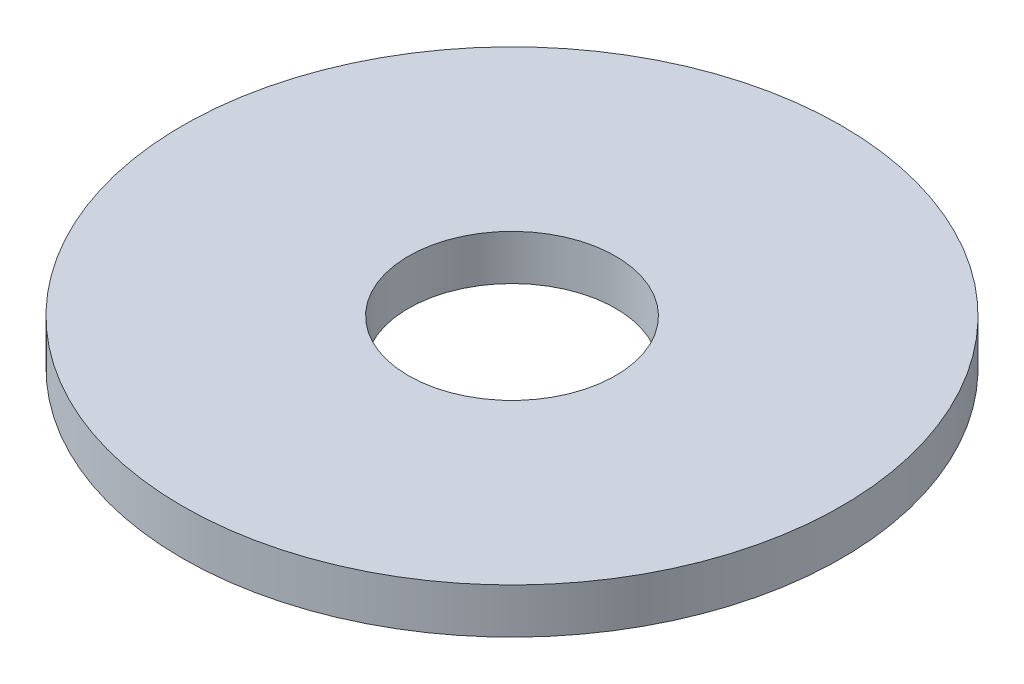
SolidWorks part; units mm, degrees
ref_plane "Front Plane" through (0, 0, 0) normal (0, 0, 1) x (1, 0, 0)
ref_plane "Top Plane" through (0, 0, 0) normal (0, 1, 0) x (1, 0, 0)
ref_plane "Right Plane" through (0, 0, 0) normal (1, 0, 0) x (0, 0, -1)
sketch "Sketch1" plane through (0, 0, 0) normal (0, 1, 0) x (1, 0, 0)
  circle A0 centre (0, 0) radius 87.5
  dimension "FLANGE_OD" = 175
extrude "Boss-Extrude1" add sketch "Sketch1" along normal blind 12
sketch "Sketch2" plane through (0, 0, 0) normal (0, 1, 0) x (1, 0, 0)
  circle A0 centre (0, 0) radius 27.5
  dimension "BORE_D" = 55
extrude "Cut-Extrude1" cut sketch "Sketch2" along normal through all
sketch "Sketch3" plane through (0, 12, 0) normal (0, 1, 0) x (1, 0, 0)
  circle A0 centre (0, 0) radius 20.168 construction
  circle A1 centre (-20.168, 0) radius 5.2138
  dimension "BOLT_D" = 10.4275
  dimension "BOLT_PCD" = 40.336
extrude "Cut-Extrude2" cut sketch "Sketch3" against normal blind 9.7605 rebuild error yes
pattern_circular "CirPattern1" count 8 over 360 rebuild error yes
